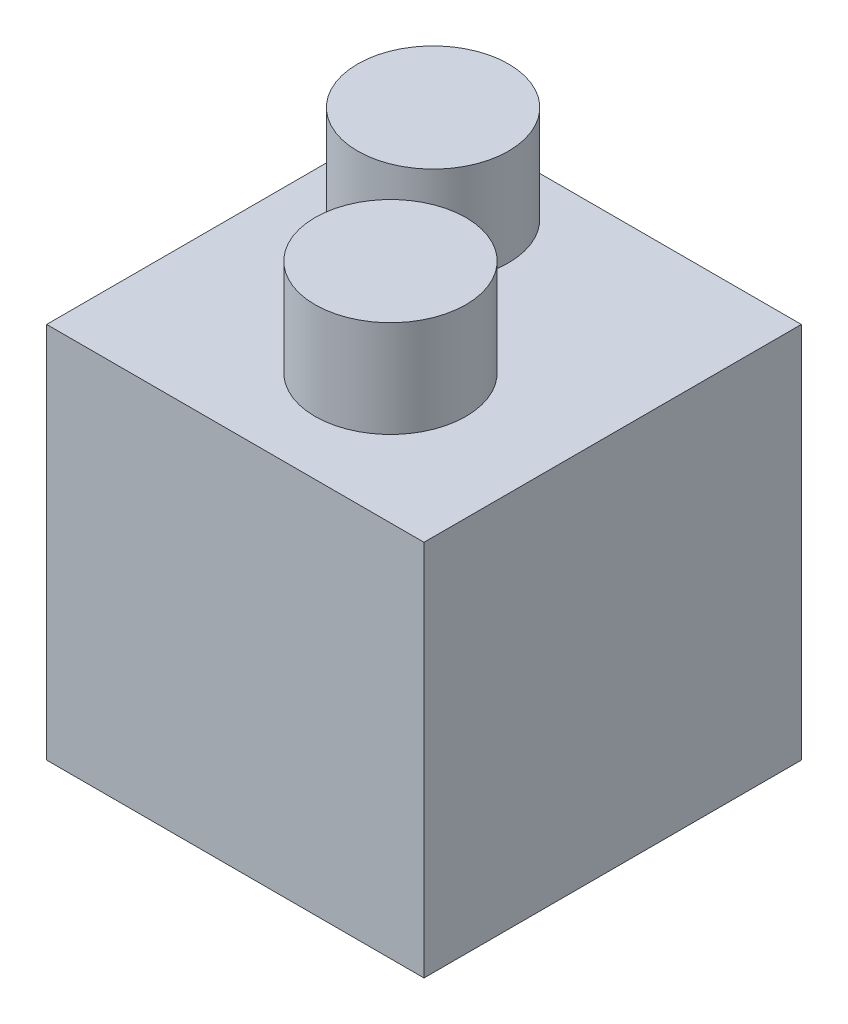
SolidWorks part; units mm, degrees
ref_plane "Plan de face" through (0, 0, 0) normal (0, 0, 1) x (1, 0, 0)
ref_plane "Plan de dessus" through (0, 0, 0) normal (0, 1, 0) x (1, 0, 0)
ref_plane "Plan de droite" through (0, 0, 0) normal (1, 0, 0) x (0, 0, -1)
sketch "Esquisse1" plane through (0, 0, 0) normal (0, 0, 1) x (1, 0, 0)
  line L1 (9.8703, 9.8703) -> (29.8703, 9.8703)
  line L2 (9.8703, 9.8703) -> (9.8703, -10.1297)
  line L3 (9.8703, -10.1297) -> (29.8703, -10.1297)
  line L4 (29.8703, 9.8703) -> (29.8703, -10.1297)
  dimension "D1" = 20
  dimension "D2" = 20
extrude "Boss.-Extru.1" add sketch "Esquisse1" along normal blind 20
sketch "Esquisse2" plane through (0, 0, 0) normal (0, 1, 0) x (1, 0, 0)
  circle A0 centre (15.2846, -4.9323) radius 4
  circle A1 centre (21.2061, -13.1122) radius 4
extrude "Boss.-Extru.2" add sketch "Esquisse2" along normal blind 5
extrude "Boss.-Extru.3" add sketch "Esquisse2<2>" along normal blind 15
sketch "Esquisse2<2>" plane through (0, 0, 0) normal (0, 1, 0) x (1, 0, 0) same geometry as "Esquisse2"
